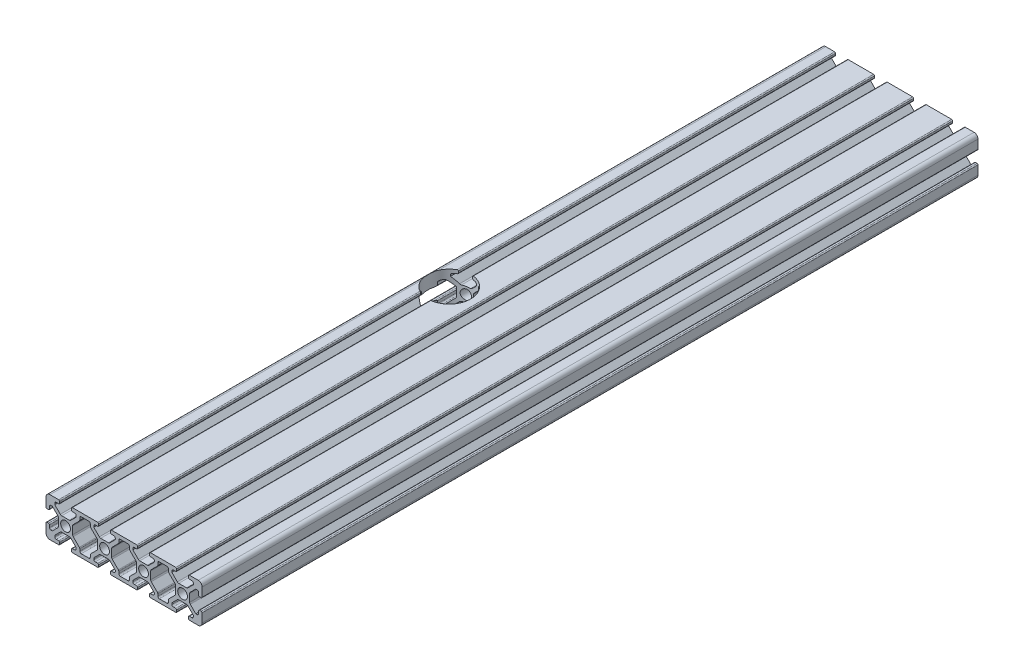
SolidWorks part; units mm, degrees
ref_plane "Front Plane" through (0, 0, 0) normal (0, 0, 1) x (1, 0, 0)
ref_plane "Top Plane" through (0, 0, 0) normal (0, 1, 0) x (1, 0, 0)
ref_plane "Right Plane" through (0, 0, 0) normal (1, 0, 0) x (0, 0, -1)
sketch "Sketch1" plane through (0, 0, 0) normal (0, 0, 1) x (1, 0, 0)
  line L0 (-33.8042, -5.2629) -> (-29.3042, -5.2629)
  line L1 (44.1958, -3.2629) -> (44.1958, 1.2371)
  line L2 (42.1958, 14.7371) -> (37.6958, 14.7371)
  line L3 (-35.8042, 12.7371) -> (-35.8042, 8.2371)
  line L4 (-2.8042, 14.2371) -> (-2.8042, 13.4371)
  line L5 (-8.8042, 14.2371) -> (-8.8042, 13.4371)
  line L6 (-28.8042, 14.2371) -> (-28.8042, 13.4371)
  line L7 (-22.8042, 14.2371) -> (-22.8042, 13.4371)
  line L8 (-29.3042, 14.7371) -> (-33.8042, 14.7371)
  line L9 (17.1958, 14.2371) -> (17.1958, 13.4371)
  line L10 (11.1958, 14.2371) -> (11.1958, 13.4371)
  line L11 (37.1958, 14.2371) -> (37.1958, 13.4371)
  line L12 (31.1958, 14.2371) -> (31.1958, 13.4371)
  line L13 (-2.8042, -3.9629) -> (-2.8042, -4.7629)
  line L14 (-8.8042, -3.9629) -> (-8.8042, -4.7629)
  line L15 (17.1958, -3.9629) -> (17.1958, -4.7629)
  line L16 (11.1958, -3.9629) -> (11.1958, -4.7629)
  line L17 (37.1958, -3.9629) -> (37.1958, -4.7629)
  line L18 (31.1958, -3.9629) -> (31.1958, -4.7629)
  line L19 (-22.8042, -3.9629) -> (-22.8042, -4.7629)
  line L20 (-28.8042, -3.9629) -> (-28.8042, -4.7629)
  line L21 (-22.3042, 14.7371) -> (-9.3042, 14.7371) construction
  line L22 (-9.3042, 14.7371) -> (-22.3042, 14.7371)
  line L23 (10.6958, 14.7371) -> (-2.3042, 14.7371)
  line L24 (30.6958, 14.7371) -> (17.6958, 14.7371)
  line L25 (37.6958, -5.2629) -> (42.1958, -5.2629)
  line L26 (17.6958, -5.2629) -> (30.6958, -5.2629)
  line L27 (-2.3042, -5.2629) -> (10.6958, -5.2629)
  line L28 (-22.3042, -5.2629) -> (-9.3042, -5.2629)
  line L29 (43.6958, 7.7371) -> (42.8958, 7.7371)
  line L30 (43.6958, 1.7371) -> (42.8958, 1.7371)
  line L31 (-35.3042, 7.7371) -> (-34.5042, 7.7371)
  line L32 (-35.3042, 1.7371) -> (-34.5042, 1.7371)
  line L33 (-35.8042, 1.2371) -> (-35.8042, -3.2629)
  line L34 (44.1958, 8.2371) -> (44.1958, 12.7371)
  line L35 (-34.0042, 8.2371) -> (-34.0042, 9.4871)
  line L36 (-30.5542, 12.9371) -> (-29.3042, 12.9371)
  line L37 (42.3958, 9.4871) -> (42.3958, 8.2371)
  line L38 (38.9458, -3.4629) -> (37.6958, -3.4629)
  line L39 (-34.0042, -0.0129) -> (-34.0042, 1.2371)
  line L40 (-22.3042, 12.9371) -> (-21.0542, 12.9371)
  line L41 (-29.3042, -3.4629) -> (-30.5542, -3.4629)
  line L42 (-2.3042, 12.9371) -> (-1.0542, 12.9371)
  line L43 (-9.3042, -3.4629) -> (-10.5542, -3.4629)
  line L44 (17.6958, 12.9371) -> (18.9458, 12.9371)
  line L45 (10.6958, -3.4629) -> (9.4458, -3.4629)
  line L46 (37.6958, 12.9371) -> (38.9458, 12.9371)
  line L47 (30.6958, -3.4629) -> (29.4458, -3.4629)
  line L48 (42.3958, 1.2371) -> (42.3958, -0.0129)
  line L49 (-23.1341, 8.68) -> (-20.3042, 11.5098)
  line L50 (-23.1341, 0.7942) -> (-20.3042, -2.0357)
  line L51 (-3.1341, 8.68) -> (-0.3042, 11.5098)
  line L52 (-1.8613, 7.4072) -> (1.2762, 10.5446)
  line L53 (-8.4743, 8.68) -> (-11.3042, 11.5098)
  line L54 (-12.8845, 10.5446) -> (-9.7471, 7.4072)
  line L55 (-8.4743, 0.7942) -> (-11.3042, -2.0357)
  line L56 (-12.8845, -1.0705) -> (-9.7471, 2.067)
  line L57 (11.5257, 8.68) -> (8.6958, 11.5098)
  line L58 (7.1155, 10.5446) -> (10.2529, 7.4072)
  line L59 (11.5257, 0.7942) -> (8.6958, -2.0357)
  line L60 (7.1155, -1.0705) -> (10.2529, 2.067)
  line L61 (31.5257, 8.68) -> (28.6958, 11.5098)
  line L62 (27.1155, 10.5446) -> (30.2529, 7.4072)
  line L63 (31.5257, 0.7942) -> (28.6958, -2.0357)
  line L64 (27.1155, -1.0705) -> (30.2529, 2.067)
  line L65 (-1.8613, 2.067) -> (1.2762, -1.0705)
  line L66 (-21.8613, 7.4072) -> (-18.7238, 10.5446)
  line L67 (-29.7471, 2.067) -> (-32.577, -0.7629)
  line L68 (-28.4743, 0.7942) -> (-31.3042, -2.0357)
  line L69 (-28.4743, 8.68) -> (-31.3042, 11.5098)
  line L70 (-3.1341, 0.7942) -> (-0.3042, -2.0357)
  line L71 (-21.8613, 2.067) -> (-18.7238, -1.0705)
  line L72 (16.8659, 8.68) -> (19.6958, 11.5098)
  line L73 (-29.7471, 7.4072) -> (-32.577, 10.2371)
  line L74 (18.1387, 7.4072) -> (21.2762, 10.5446)
  line L75 (18.1387, 2.067) -> (21.2762, -1.0705)
  line L76 (16.8659, 0.7942) -> (19.6958, -2.0357)
  line L77 (36.8659, 8.68) -> (39.6958, 11.5098)
  line L78 (38.1387, 7.4072) -> (40.9686, 10.2371)
  line L79 (38.1387, 2.067) -> (40.9686, -0.7629)
  line L80 (36.8659, 0.7942) -> (39.6958, -2.0357)
  line L81 (-7.7672, 8.3871) -> (-3.8412, 8.3871)
  line L82 (-17.7542, 12.9371) -> (-13.8542, 12.9371)
  line L83 (-21.0542, -3.4629) -> (-22.3042, -3.4629)
  line L84 (-20.3042, 12.1871) -> (-20.3042, 11.5098)
  line L85 (-1.0542, -3.4629) -> (-2.3042, -3.4629)
  line L86 (-31.3042, 12.1871) -> (-31.3042, 11.5098)
  line L87 (18.9458, -3.4629) -> (17.6958, -3.4629)
  line L88 (-11.3042, 12.1871) -> (-11.3042, 11.5098)
  line L89 (-10.5542, 12.9371) -> (-9.3042, 12.9371)
  line L90 (9.4458, 12.9371) -> (10.6958, 12.9371)
  line L91 (-2.1542, 6.7001) -> (-2.1542, 2.7741)
  line L92 (-3.8412, 1.0871) -> (-7.7672, 1.0871)
  line L93 (-9.4542, 2.7741) -> (-9.4542, 6.7001)
  line L94 (29.4458, 12.9371) -> (30.6958, 12.9371)
  line L95 (8.6958, 12.1871) -> (8.6958, 11.5098)
  line L96 (-0.3042, 12.1871) -> (-0.3042, 11.5098)
  line L97 (-22.1542, 6.7001) -> (-22.1542, 2.7741)
  line L98 (-23.8412, 1.0871) -> (-27.7672, 1.0871)
  line L99 (-29.4542, 2.7741) -> (-29.4542, 6.7001)
  line L100 (-27.7672, 8.3871) -> (-23.8412, 8.3871)
  line L101 (12.2328, 8.3871) -> (16.1588, 8.3871)
  line L102 (17.8458, 6.7001) -> (17.8458, 2.7741)
  line L103 (16.1588, 1.0871) -> (12.2328, 1.0871)
  line L104 (10.5458, 2.7741) -> (10.5458, 6.7001)
  line L105 (32.2328, 8.3871) -> (36.1588, 8.3871)
  line L106 (37.8458, 6.7001) -> (37.8458, 2.7741)
  line L107 (36.1588, 1.0871) -> (32.2328, 1.0871)
  line L108 (30.5458, 2.7741) -> (30.5458, 6.7001)
  line L109 (28.6958, 12.1871) -> (28.6958, 11.5098)
  line L110 (19.6958, 12.1871) -> (19.6958, 11.5098)
  line L111 (-31.3042, -2.7129) -> (-31.3042, -2.0357)
  line L112 (39.6958, 12.1871) -> (39.6958, 11.5098)
  line L113 (-11.3042, -2.7129) -> (-11.3042, -2.0357)
  line L114 (-20.3042, -2.7129) -> (-20.3042, -2.0357)
  line L115 (8.6958, -2.7129) -> (8.6958, -2.0357)
  line L116 (-0.3042, -2.7129) -> (-0.3042, -2.0357)
  line L117 (28.6958, -2.7129) -> (28.6958, -2.0357)
  line L118 (19.6958, -2.7129) -> (19.6958, -2.0357)
  line L119 (-33.2542, 10.2371) -> (-32.577, 10.2371)
  line L120 (39.6958, -2.7129) -> (39.6958, -2.0357)
  line L121 (-33.2542, -0.7629) -> (-32.577, -0.7629)
  line L122 (41.6458, 10.2371) -> (40.9686, 10.2371)
  line L123 (-18.5042, 12.1871) -> (-18.5042, 11.0749)
  line L124 (41.6458, -0.7629) -> (40.9686, -0.7629)
  line L125 (-13.1042, 12.1871) -> (-13.1042, 11.0749)
  line L126 (2.2458, 12.9371) -> (6.1458, 12.9371)
  line L127 (1.4958, 12.1871) -> (1.4958, 11.0749)
  line L128 (6.8958, 12.1871) -> (6.8958, 11.0749)
  line L129 (22.2458, 12.9371) -> (26.1458, 12.9371)
  line L130 (21.4958, 12.1871) -> (21.4958, 11.0749)
  line L131 (26.8958, 12.1871) -> (26.8958, 11.0749)
  line L132 (-18.5042, -1.6008) -> (-18.5042, -2.7129)
  line L133 (-17.7542, -3.4629) -> (-13.8542, -3.4629)
  line L134 (-13.1042, -2.7129) -> (-13.1042, -1.6008)
  line L135 (1.4958, -1.6008) -> (1.4958, -2.7129)
  line L136 (2.2458, -3.4629) -> (6.1458, -3.4629)
  line L137 (6.8958, -2.7129) -> (6.8958, -1.6008)
  line L138 (21.4958, -1.6008) -> (21.4958, -2.7129)
  line L139 (22.2458, -3.4629) -> (26.1458, -3.4629)
  line L140 (26.8958, -2.7129) -> (26.8958, -1.6008)
  circle A0 centre (-25.8042, 4.7371) radius 2.5
  circle A1 centre (-5.8042, 4.7371) radius 2.5
  circle A2 centre (14.1958, 4.7371) radius 2.5
  circle A3 centre (34.1958, 4.7371) radius 2.5
  arc A4 (42.1958, -5.2629) -> (44.1958, -3.2629) centre (42.1958, -3.2629) ccw
  arc A5 (44.1958, 12.7371) -> (42.1958, 14.7371) centre (42.1958, 12.7371) ccw
  arc A6 (-33.8042, -5.2629) -> (-35.8042, -3.2629) centre (-33.8042, -3.2629) cw
  arc A7 (-33.8042, 14.7371) -> (-35.8042, 12.7371) centre (-33.8042, 12.7371) ccw
  arc A8 (-23.1341, 8.68) -> (-23.8412, 8.3871) centre (-23.8412, 9.3871) cw
  arc A9 (-28.4743, 8.68) -> (-27.7672, 8.3871) centre (-27.7672, 9.3871) ccw
  arc A10 (-29.7471, 7.4072) -> (-29.4542, 6.7001) centre (-30.4542, 6.7001) cw
  arc A11 (-29.7471, 2.067) -> (-29.4542, 2.7741) centre (-30.4542, 2.7741) ccw
  arc A12 (-28.4743, 0.7942) -> (-27.7672, 1.0871) centre (-27.7672, 0.0871) cw
  arc A13 (-23.1341, 0.7942) -> (-23.8412, 1.0871) centre (-23.8412, 0.0871) ccw
  arc A14 (-3.1341, 0.7942) -> (-3.8412, 1.0871) centre (-3.8412, 0.0871) ccw
  arc A15 (-8.4743, 0.7942) -> (-7.7672, 1.0871) centre (-7.7672, 0.0871) cw
  arc A16 (-8.4743, 8.68) -> (-7.7672, 8.3871) centre (-7.7672, 9.3871) ccw
  arc A17 (-3.1341, 8.68) -> (-3.8412, 8.3871) centre (-3.8412, 9.3871) cw
  arc A18 (11.5257, 0.7942) -> (12.2328, 1.0871) centre (12.2328, 0.0871) cw
  arc A19 (16.8659, 0.7942) -> (16.1588, 1.0871) centre (16.1588, 0.0871) ccw
  arc A20 (16.8659, 8.68) -> (16.1588, 8.3871) centre (16.1588, 9.3871) cw
  arc A21 (11.5257, 8.68) -> (12.2328, 8.3871) centre (12.2328, 9.3871) ccw
  arc A22 (36.8659, 8.68) -> (36.1588, 8.3871) centre (36.1588, 9.3871) cw
  arc A23 (31.5257, 8.68) -> (32.2328, 8.3871) centre (32.2328, 9.3871) ccw
  arc A24 (31.5257, 0.7942) -> (32.2328, 1.0871) centre (32.2328, 0.0871) cw
  arc A25 (36.8659, 0.7942) -> (36.1588, 1.0871) centre (36.1588, 0.0871) ccw
  arc A26 (38.1387, 2.067) -> (37.8458, 2.7741) centre (38.8458, 2.7741) cw
  arc A27 (38.1387, 7.4072) -> (37.8458, 6.7001) centre (38.8458, 6.7001) ccw
  arc A28 (30.2529, 2.067) -> (30.5458, 2.7741) centre (29.5458, 2.7741) ccw
  arc A29 (30.2529, 7.4072) -> (30.5458, 6.7001) centre (29.5458, 6.7001) cw
  arc A30 (18.1387, 2.067) -> (17.8458, 2.7741) centre (18.8458, 2.7741) cw
  arc A31 (18.1387, 7.4072) -> (17.8458, 6.7001) centre (18.8458, 6.7001) ccw
  arc A32 (42.3958, 9.4871) -> (41.6458, 10.2371) centre (41.6458, 9.4871) ccw
  arc A33 (39.6958, 12.1871) -> (38.9458, 12.9371) centre (38.9458, 12.1871) ccw
  arc A34 (42.3958, -0.0129) -> (41.6458, -0.7629) centre (41.6458, -0.0129) cw
  arc A35 (39.6958, -2.7129) -> (38.9458, -3.4629) centre (38.9458, -2.7129) cw
  arc A36 (10.2529, 2.067) -> (10.5458, 2.7741) centre (9.5458, 2.7741) ccw
  arc A37 (10.2529, 7.4072) -> (10.5458, 6.7001) centre (9.5458, 6.7001) cw
  arc A38 (-1.8613, 2.067) -> (-2.1542, 2.7741) centre (-1.1542, 2.7741) cw
  arc A39 (-1.8613, 7.4072) -> (-2.1542, 6.7001) centre (-1.1542, 6.7001) ccw
  arc A40 (-21.8613, 7.4072) -> (-22.1542, 6.7001) centre (-21.1542, 6.7001) ccw
  arc A41 (-21.8613, 2.067) -> (-22.1542, 2.7741) centre (-21.1542, 2.7741) cw
  arc A42 (-9.7471, 2.067) -> (-9.4542, 2.7741) centre (-10.4542, 2.7741) ccw
  arc A43 (-9.7471, 7.4072) -> (-9.4542, 6.7001) centre (-10.4542, 6.7001) cw
  arc A44 (29.4458, -3.4629) -> (28.6958, -2.7129) centre (29.4458, -2.7129) cw
  arc A45 (26.1458, -3.4629) -> (26.8958, -2.7129) centre (26.1458, -2.7129) ccw
  arc A46 (21.4958, -2.7129) -> (22.2458, -3.4629) centre (22.2458, -2.7129) ccw
  arc A47 (18.9458, -3.4629) -> (19.6958, -2.7129) centre (18.9458, -2.7129) ccw
  arc A48 (9.4458, -3.4629) -> (8.6958, -2.7129) centre (9.4458, -2.7129) cw
  arc A49 (28.6958, 12.1871) -> (29.4458, 12.9371) centre (29.4458, 12.1871) cw
  arc A50 (26.1458, 12.9371) -> (26.8958, 12.1871) centre (26.1458, 12.1871) cw
  arc A51 (22.2458, 12.9371) -> (21.4958, 12.1871) centre (22.2458, 12.1871) ccw
  arc A52 (17.1958, 13.4371) -> (17.6958, 12.9371) centre (17.6958, 13.4371) ccw
  arc A53 (17.1958, 14.2371) -> (17.6958, 14.7371) centre (17.6958, 14.2371) cw
  arc A54 (31.1958, 13.4371) -> (30.6958, 12.9371) centre (30.6958, 13.4371) cw
  arc A55 (31.1958, 14.2371) -> (30.6958, 14.7371) centre (30.6958, 14.2371) ccw
  arc A56 (37.1958, 13.4371) -> (37.6958, 12.9371) centre (37.6958, 13.4371) ccw
  arc A57 (37.1958, 14.2371) -> (37.6958, 14.7371) centre (37.6958, 14.2371) cw
  arc A58 (42.8958, 7.7371) -> (42.3958, 8.2371) centre (42.8958, 8.2371) cw
  arc A59 (43.6958, 7.7371) -> (44.1958, 8.2371) centre (43.6958, 8.2371) ccw
  arc A60 (42.8958, 1.7371) -> (42.3958, 1.2371) centre (42.8958, 1.2371) ccw
  arc A61 (43.6958, 1.7371) -> (44.1958, 1.2371) centre (43.6958, 1.2371) cw
  arc A62 (37.1958, -4.7629) -> (37.6958, -5.2629) centre (37.6958, -4.7629) ccw
  arc A63 (37.1958, -3.9629) -> (37.6958, -3.4629) centre (37.6958, -3.9629) cw
  arc A64 (31.1958, -4.7629) -> (30.6958, -5.2629) centre (30.6958, -4.7629) cw
  arc A65 (31.1958, -3.9629) -> (30.6958, -3.4629) centre (30.6958, -3.9629) ccw
  arc A66 (17.1958, -4.7629) -> (17.6958, -5.2629) centre (17.6958, -4.7629) ccw
  arc A67 (17.1958, -3.9629) -> (17.6958, -3.4629) centre (17.6958, -3.9629) cw
  arc A68 (11.1958, -4.7629) -> (10.6958, -5.2629) centre (10.6958, -4.7629) cw
  arc A69 (11.1958, -3.9629) -> (10.6958, -3.4629) centre (10.6958, -3.9629) ccw
  arc A70 (-2.8042, -4.7629) -> (-2.3042, -5.2629) centre (-2.3042, -4.7629) ccw
  arc A71 (-2.8042, -3.9629) -> (-2.3042, -3.4629) centre (-2.3042, -3.9629) cw
  arc A72 (-8.8042, -4.7629) -> (-9.3042, -5.2629) centre (-9.3042, -4.7629) cw
  arc A73 (-8.8042, -3.9629) -> (-9.3042, -3.4629) centre (-9.3042, -3.9629) ccw
  arc A74 (11.1958, 13.4371) -> (10.6958, 12.9371) centre (10.6958, 13.4371) cw
  arc A75 (11.1958, 14.2371) -> (10.6958, 14.7371) centre (10.6958, 14.2371) ccw
  arc A76 (-2.8042, 13.4371) -> (-2.3042, 12.9371) centre (-2.3042, 13.4371) ccw
  arc A77 (-2.8042, 14.2371) -> (-2.3042, 14.7371) centre (-2.3042, 14.2371) cw
  arc A78 (-8.8042, 13.4371) -> (-9.3042, 12.9371) centre (-9.3042, 13.4371) cw
  arc A79 (-8.8042, 14.2371) -> (-9.3042, 14.7371) centre (-9.3042, 14.2371) ccw
  arc A80 (-22.8042, 13.4371) -> (-22.3042, 12.9371) centre (-22.3042, 13.4371) ccw
  arc A81 (-22.3042, 14.7371) -> (-22.8042, 14.2371) centre (-22.3042, 14.2371) ccw
  arc A82 (-22.8042, -4.7629) -> (-22.3042, -5.2629) centre (-22.3042, -4.7629) ccw
  arc A83 (-22.8042, -3.9629) -> (-22.3042, -3.4629) centre (-22.3042, -3.9629) cw
  arc A84 (-28.8042, -4.7629) -> (-29.3042, -5.2629) centre (-29.3042, -4.7629) cw
  arc A85 (-28.8042, -3.9629) -> (-29.3042, -3.4629) centre (-29.3042, -3.9629) ccw
  arc A86 (-35.8042, 1.2371) -> (-35.3042, 1.7371) centre (-35.3042, 1.2371) cw
  arc A87 (-34.5042, 1.7371) -> (-34.0042, 1.2371) centre (-34.5042, 1.2371) cw
  arc A88 (-35.8042, 8.2371) -> (-35.3042, 7.7371) centre (-35.3042, 8.2371) ccw
  arc A89 (-34.5042, 7.7371) -> (-34.0042, 8.2371) centre (-34.5042, 8.2371) ccw
  arc A90 (-29.3042, 14.7371) -> (-28.8042, 14.2371) centre (-29.3042, 14.2371) cw
  arc A91 (-28.8042, 13.4371) -> (-29.3042, 12.9371) centre (-29.3042, 13.4371) cw
  arc A92 (19.6958, 12.1871) -> (18.9458, 12.9371) centre (18.9458, 12.1871) ccw
  arc A93 (8.6958, 12.1871) -> (9.4458, 12.9371) centre (9.4458, 12.1871) cw
  arc A94 (1.4958, -2.7129) -> (2.2458, -3.4629) centre (2.2458, -2.7129) ccw
  arc A95 (2.2458, 12.9371) -> (1.4958, 12.1871) centre (2.2458, 12.1871) ccw
  arc A96 (6.1458, 12.9371) -> (6.8958, 12.1871) centre (6.1458, 12.1871) cw
  arc A97 (6.1458, -3.4629) -> (6.8958, -2.7129) centre (6.1458, -2.7129) ccw
  arc A98 (-1.0542, -3.4629) -> (-0.3042, -2.7129) centre (-1.0542, -2.7129) ccw
  arc A99 (-10.5542, -3.4629) -> (-11.3042, -2.7129) centre (-10.5542, -2.7129) cw
  arc A100 (-21.0542, -3.4629) -> (-20.3042, -2.7129) centre (-21.0542, -2.7129) ccw
  arc A101 (-30.5542, -3.4629) -> (-31.3042, -2.7129) centre (-30.5542, -2.7129) cw
  arc A102 (-33.2542, -0.7629) -> (-34.0042, -0.0129) centre (-33.2542, -0.0129) cw
  arc A103 (-34.0042, 9.4871) -> (-33.2542, 10.2371) centre (-33.2542, 9.4871) cw
  arc A104 (-11.3042, 12.1871) -> (-10.5542, 12.9371) centre (-10.5542, 12.1871) cw
  arc A105 (-1.0542, 12.9371) -> (-0.3042, 12.1871) centre (-1.0542, 12.1871) cw
  arc A106 (-13.8542, 12.9371) -> (-13.1042, 12.1871) centre (-13.8542, 12.1871) cw
  arc A107 (-17.7542, 12.9371) -> (-18.5042, 12.1871) centre (-17.7542, 12.1871) ccw
  arc A108 (-20.3042, 12.1871) -> (-21.0542, 12.9371) centre (-21.0542, 12.1871) ccw
  arc A109 (-30.5542, 12.9371) -> (-31.3042, 12.1871) centre (-30.5542, 12.1871) ccw
  arc A110 (26.8958, -1.6008) -> (27.1155, -1.0705) centre (27.6458, -1.6008) cw
  arc A111 (21.4958, -1.6008) -> (21.2762, -1.0705) centre (20.7458, -1.6008) ccw
  arc A112 (26.8958, 11.0749) -> (27.1155, 10.5446) centre (27.6458, 11.0749) ccw
  arc A113 (21.4958, 11.0749) -> (21.2762, 10.5446) centre (20.7458, 11.0749) cw
  arc A114 (6.8958, -1.6008) -> (7.1155, -1.0705) centre (7.6458, -1.6008) cw
  arc A115 (1.4958, -1.6008) -> (1.2762, -1.0705) centre (0.7458, -1.6008) ccw
  arc A116 (6.8958, 11.0749) -> (7.1155, 10.5446) centre (7.6458, 11.0749) ccw
  arc A117 (1.4958, 11.0749) -> (1.2762, 10.5446) centre (0.7458, 11.0749) cw
  arc A118 (-13.1042, 11.0749) -> (-12.8845, 10.5446) centre (-12.3542, 11.0749) ccw
  arc A119 (-18.5042, 11.0749) -> (-18.7238, 10.5446) centre (-19.2542, 11.0749) cw
  arc A120 (-18.5042, -1.6008) -> (-18.7238, -1.0705) centre (-19.2542, -1.6008) ccw
  arc A121 (-13.1042, -1.6008) -> (-12.8845, -1.0705) centre (-12.3542, -1.6008) cw
  arc A122 (-13.8542, -3.4629) -> (-13.1042, -2.7129) centre (-13.8542, -2.7129) ccw
  arc A123 (-18.5042, -2.7129) -> (-17.7542, -3.4629) centre (-17.7542, -2.7129) ccw
  point P388 (0, 0)
  point P390 (0, 0)
  point P391 (0, 0)
extrude "Boss-Extrude1" add sketch "Sketch1" along normal blind 397.66
sketch "Sketch2" plane through (0, 14.7371, 0) normal (0, 1, 0) x (1, 0, 0)
  circle A0 centre (-23.8042, -202.9969) radius 11
extrude "Cut-Extrude6" cut sketch "Sketch2" against normal blind 20
